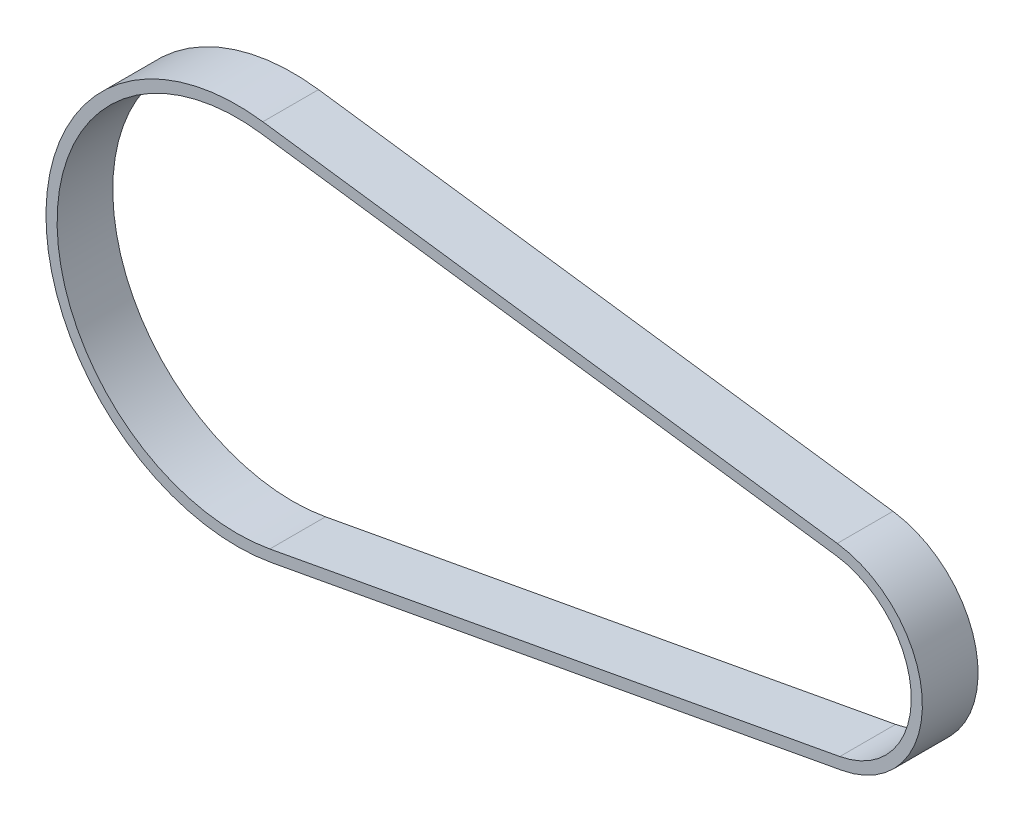
SolidWorks part; units mm, degrees
material "Rubber"
ref_plane "Front Plane" through (0, 0, 0) normal (0, 0, 1) x (1, 0, 0)
ref_plane "Top Plane" through (0, 0, 0) normal (0, 1, 0) x (1, 0, 0)
ref_plane "Right Plane" through (0, 0, 0) normal (1, 0, 0) x (0, 0, -1)
sketch "Sketch2" plane through (0, 0, 0) normal (0, 0, 1) x (1, 0, 0)
  line L0 (0, 0) -> (1, 0) construction
  line L1 (0, 0) -> (0, 1) construction
  line L2 (6.9277, 51.0319) -> (161.6592, 30.0267)
  line L3 (162.906, -22.2919) -> (9.3508, -50.644)
  arc A0 (9.3508, -50.644) -> (6.9277, 51.0319) centre (0, 0) cw
  arc A1 (161.6592, 30.0267) -> (162.906, -22.2919) centre (158.0945, 3.7676) cw
sketch "Sketch3" plane through (0, 0, 0) normal (0, 0, 1) x (1, 0, 0)
  line L0 (161.6592, 30.0267) -> (6.9277, 51.0319)
  line L1 (9.3508, -50.644) -> (162.906, -22.2919)
  line L2 (161.2557, 27.054) -> (6.5241, 48.0592)
  line L3 (8.8061, -47.6938) -> (162.3613, -19.3418)
  arc A0 (6.9277, 51.0319) -> (9.3508, -50.644) centre (0, 0) ccw
  arc A1 (162.906, -22.2919) -> (161.6592, 30.0267) centre (158.0945, 3.7676) ccw
  arc A2 (6.5241, 48.0592) -> (8.8061, -47.6938) centre (0, 0) ccw
  arc A3 (162.3613, -19.3418) -> (161.2557, 27.054) centre (158.0945, 3.7676) ccw
  dimension "D1" = 3
extrude "Boss-Extrude1" add sketch "Sketch3" along normal blind 7.5 and the other way blind 7.5
